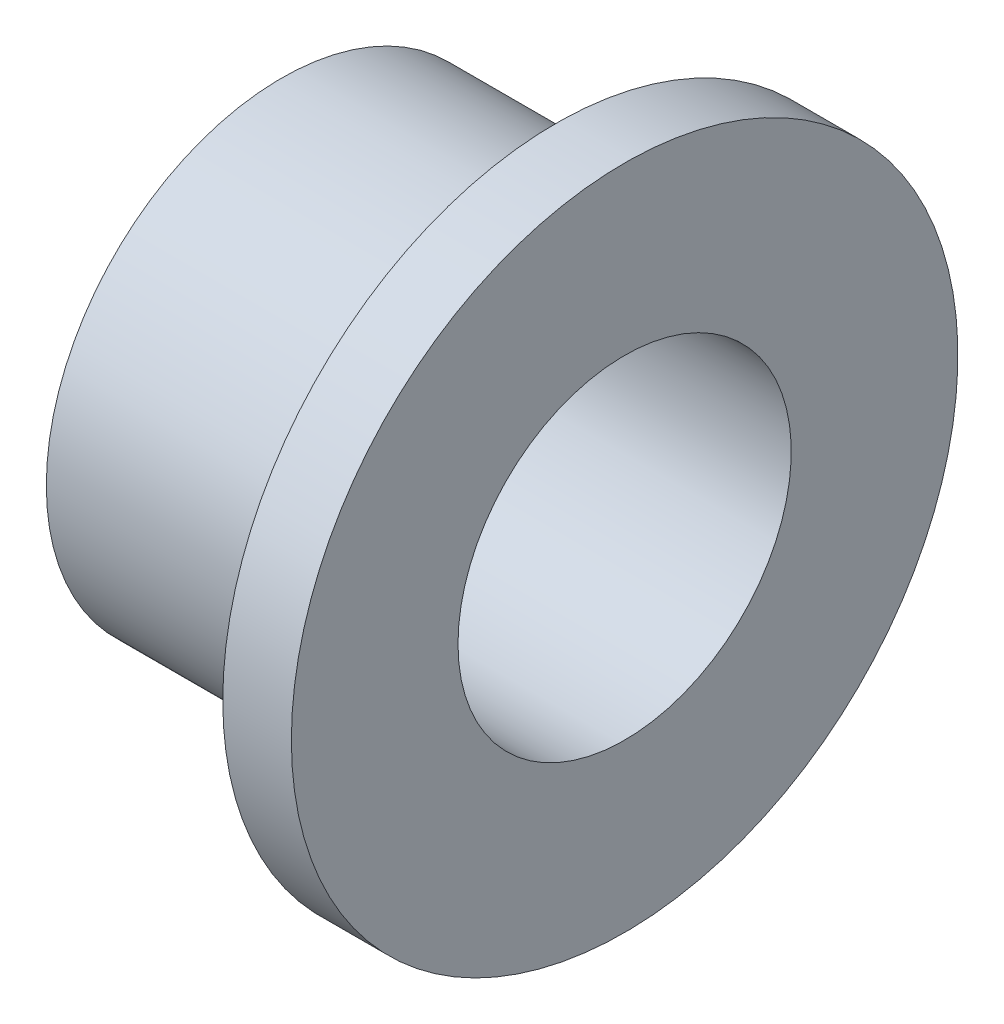
SolidWorks part; units mm, degrees
ref_plane "Front Plane" through (0, 0, 0) normal (0, 0, 1) x (1, 0, 0)
ref_plane "Top Plane" through (0, 0, 0) normal (0, 1, 0) x (1, 0, 0)
ref_plane "Right Plane" through (0, 0, 0) normal (1, 0, 0) x (0, 0, -1)
sketch "Sketch1" plane through (0, 0, 0) normal (0, 1, 0) x (1, 0, 0)
  line L0 (-56.3758, 0) -> (63.0336, 0) construction
  line L1 (-30.1745, 0) -> (-30.1745, -24) construction
  line L2 (-30.1745, -24) -> (-2.1745, -24)
  line L3 (-2.1745, -24) -> (-2.1745, -34)
  line L4 (-2.1745, -34) -> (4.8255, -34)
  line L5 (4.8255, -34) -> (4.8255, -17)
  line L6 (4.8255, -17) -> (-30.1745, -17)
  line L7 (-30.1745, -17) -> (-30.1745, -24)
  dimension "D1" = 24
  dimension "D2" = 17
  dimension "D3" = 35
  dimension "D4" = 28
  dimension "D5" = 34
revolve "Revolve1" add sketch "Sketch1" angle 360 about L0
ref_axis "Axis1" through (4.8255, 0, 0) along (-1, 0, 0)
